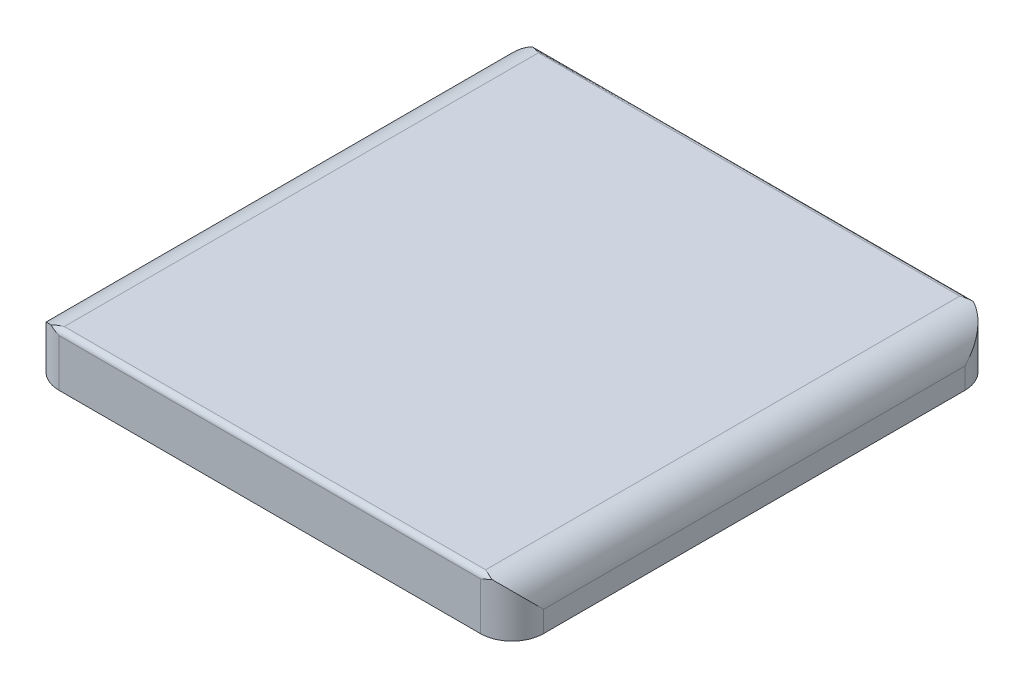
SolidWorks part; units mm, degrees
material "ABS"
ref_plane "Front Plane" through (0, 0, 0) normal (0, 0, 1) x (1, 0, 0)
ref_plane "Top Plane" through (0, 0, 0) normal (0, 1, 0) x (1, 0, 0)
ref_plane "Right Plane" through (0, 0, 0) normal (1, 0, 0) x (0, 0, -1)
sketch "Sketch2" plane through (0, 0, 0) normal (0, 1, 0) x (1, 0, 0)
  line L1 (-50.8, -58.42) -> (50.8, -58.42)
  line L2 (-58.42, -50.8) -> (-58.42, 50.8)
  line L3 (-50.8, 58.42) -> (50.8, 58.42)
  line L4 (58.42, -50.8) -> (58.42, 50.8)
  line L5 (-58.42, -58.42) -> (58.42, 58.42) construction
  line L6 (-58.42, 58.42) -> (58.42, -58.42) construction
  arc A0 (50.8, -58.42) -> (58.42, -50.8) centre (50.8, -50.8) ccw
  arc A1 (58.42, 50.8) -> (50.8, 58.42) centre (50.8, 50.8) ccw
  arc A2 (-50.8, 58.42) -> (-58.42, 50.8) centre (-50.8, 50.8) ccw
  arc A3 (-58.42, -50.8) -> (-50.8, -58.42) centre (-50.8, -50.8) ccw
  point P0 (0, 0)
  dimension "D1" = 7.62
extrude "Boss-Extrude1" add sketch "Sketch2" along normal blind 12.7
fillet "Fillet1" radius 7.62 2 edges at (58.42, 12.7, 0) (-58.42, 12.7, 0)
fillet "Fillet3" radius 1.27 2 edges at (0, 12.7, -58.42) (0, 12.7, 58.42)
shell "Shell1" thickness 1.778
